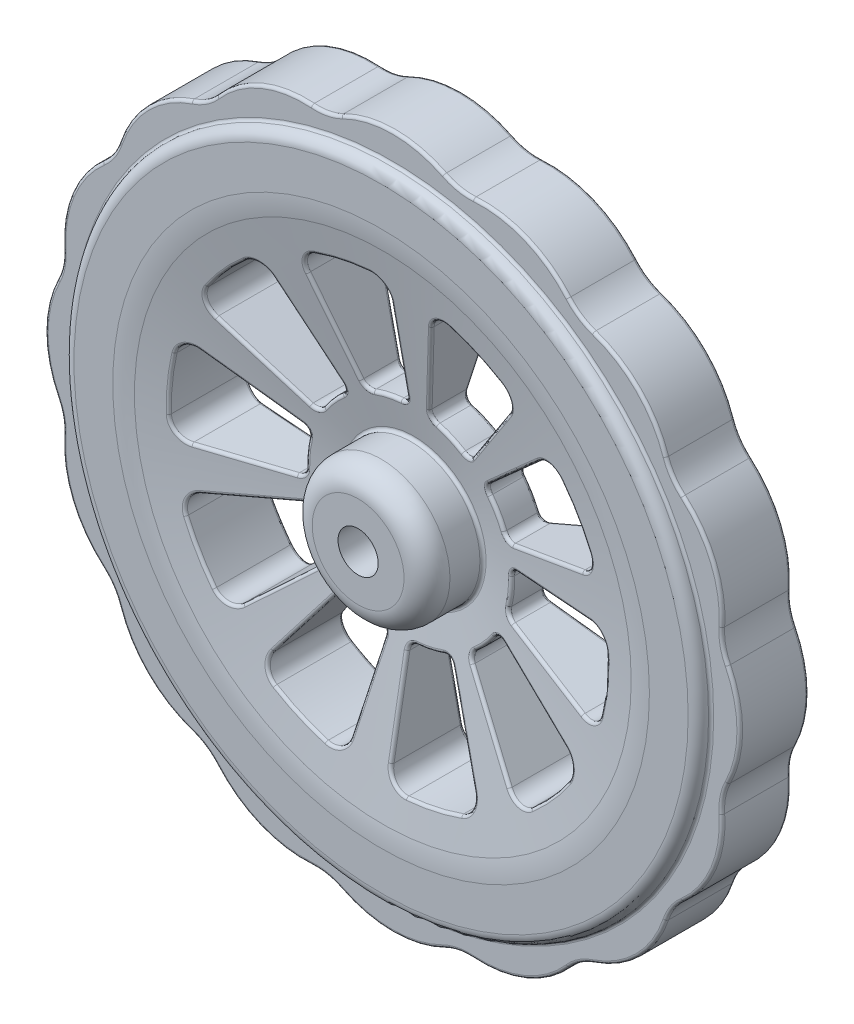
SolidWorks part; units mm, degrees
ref_plane "Alzado" through (0, 0, 0) normal (0, 0, 1) x (1, 0, 0)
ref_plane "Planta" through (0, 0, 0) normal (0, 1, 0) x (1, 0, 0)
ref_plane "Vista lateral" through (0, 0, 0) normal (1, 0, 0) x (0, 0, -1)
sketch "Croquis1" plane through (0, 0, 0) normal (0, 0, 1) x (1, 0, 0)
  circle A1 centre (0, 0) radius 27.75
  dimension "D2" = 55.5
extrude "Saliente-Extruir1" add sketch "Croquis1" along normal blind 8
fillet "Redondeo1" radius 1 2 edges at (27.75, 0, 8) (27.75, 0, 0)
ref_plane "Plano1" through (0, 0, 4) normal (0, 0, 1) x (1, 0, 0)
sketch "Croquis3" plane through (0, 0, 4) normal (0, 0, 1) x (1, 0, 0)
  line L0 (0, 0) -> (0, 10.25) construction
  line L1 (0, 24.3347) -> (0, 27.75) construction
  arc A1 (9.7923, 22.2776) -> (-9.7923, 22.2776) centre (0, 20.25) ccw
  arc A3 (9.7923, 22.2776) -> (-9.7923, 22.2776) centre (0, 0) ccw
  dimension "D1" = 20
extrude "Saliente-Extruir2" add sketch "Croquis3" along normal blind 3 and the other way blind 3
pattern_circular "MatrizC1" count 16 over 360 about axis through (0, 0, 0) along (0, 0, 1) of "Saliente-Extruir2"
fillet "Redondeo2" radius 5 16 edges at (-28.4893, 5.6669, 4) (-28.4893, -5.6669, 4) (-24.1521, -16.1379, 4) (-16.1379, -24.1521, 4) (-5.6669, -28.4893, 4) (5.6669, -28.4893, 4) (16.1379, -24.1521, 4) (24.1521, -16.1379, 4) (28.4893, -5.6669, 4) (28.4893, 5.6669, 4) (24.1521, 16.1379, 4) (16.1379, 24.1521, 4) (5.6669, 28.4893, 4) (-5.6669, 28.4893, 4) (-16.1379, 24.1521, 4) (-24.1521, 16.1379, 4)
sketch "Croquis5" plane through (0, 0, 8) normal (0, 0, 1) x (1, 0, 0)
  circle A0 centre (0, 0) radius 22.5
extrude "Cortar-Extruir1" cut sketch "Croquis5" against normal blind 35 draft 80
sketch "Croquis6" plane through (0, 0, 0) normal (0, 0, -1) x (-1, 0, 0)
  circle A2 centre (0.0467, 0.0871) radius 22.5
  point P5 (0, 0)
  dimension "D1" = 45
extrude "Cortar-Extruir2" cut sketch "Croquis6" against normal blind 35 draft 80
fillet "Redondeo3" radius 10 2 edges at (-22.5467, 0.0871, 0) (22.5, 0, 8)
sketch "Croquis7" plane through (0, 0, 0) normal (0, 0, 1) x (1, 0, 0)
  circle A0 centre (0, 0) radius 6
  dimension "D1" = 12
extrude "Saliente-Extruir4" add sketch "Croquis7" along normal blind 10
sketch "Croquis8" plane through (0, 0, 10) normal (0, 0, 1) x (1, 0, 0)
  circle A0 centre (0, 0) radius 1.75
  dimension "D1" = 3.5
extrude "Cortar-Extruir3" cut sketch "Croquis8" against normal through all
sketch "Croquis9" plane through (0, 0, 8) normal (0, 0, 1) x (1, 0, 0)
  line L0 (-7.2605, 15.9427) -> (-4.0102, 8.8055)
  line L1 (0, 9.6757) -> (0, 17.5181)
  arc A0 (-0.692, 8.9279) -> (-3.0704, 8.4119) centre (0, 0) ccw
  arc A1 (-1.6249, 19.01) -> (-6.4001, 17.9739) centre (0, 0) ccw
  arc A2 (-6.4001, 17.9739) -> (-7.2605, 15.9427) centre (-5.8978, 16.5633) ccw
  arc A3 (0, 17.5181) -> (-1.6249, 19.01) centre (-1.4974, 17.5181) ccw
  arc A4 (-0.692, 8.9279) -> (0, 9.6757) centre (-0.75, 9.6757) ccw
  arc A5 (-4.0102, 8.8055) -> (-3.0704, 8.4119) centre (-3.3276, 9.1164) ccw
  dimension "D1" = 1.5
extrude "Cortar-Extruir4" cut sketch "Croquis9" against normal blind 10
pattern_circular "MatrizC2" count 10 over 360 about axis through (0, 0, 0) along (0, 0, 1) of "Cortar-Extruir4"
fillet "Redondeo4" radius 0.25 66 edges at (-27.9474, -11.5762, 7) (-27.9474, -11.5762, 1) (-21.39, -21.39, 7) (-21.39, -21.39, 1) (-11.5762, -27.9474, 7) (-11.5762, -27.9474, 1) (0, -30.25, 7) (0, -30.25, 1) (11.5762, -27.9474, 7) (11.5762, -27.9474, 1) (21.39, -21.39, 7) (21.39, -21.39, 1) (27.9474, -11.5762, 7) (27.9474, -11.5762, 1) (30.25, 0, 7) (30.25, 0, 1) (27.9474, 11.5762, 7) (27.9474, 11.5762, 1) (21.39, 21.39, 7) (21.39, 21.39, 1) (11.5762, 27.9474, 1) (11.5762, 27.9474, 7) (0, 30.25, 7) (0, 30.25, 1) (-11.5762, 27.9474, 7) (-11.5762, 27.9474, 1) (-21.39, 21.39, 7) (-21.39, 21.39, 1) (-28.7677, 5.7223, 1) (-28.7677, 5.7223, 7) (-28.7677, -5.7223, 1) (-28.7677, -5.7223, 7) (-24.3881, -16.2956, 1) (-24.3881, -16.2956, 7) (-16.2956, -24.3881, 1) (-16.2956, -24.3881, 7) (-5.7223, -28.7677, 1) (-5.7223, -28.7677, 7) (5.7223, -28.7677, 1) (5.7223, -28.7677, 7) (16.2956, -24.3881, 1) (16.2956, -24.3881, 7) (24.3881, -16.2956, 1) (24.3881, -16.2956, 7) (28.7677, -5.7223, 1) (28.7677, -5.7223, 7) (28.7677, 5.7223, 1) (28.7677, 5.7223, 7) (24.3881, 16.2956, 1) (24.3881, 16.2956, 7) (16.2956, 24.3881, 1) (16.2956, 24.3881, 7) (5.7223, 28.7677, 7) (5.7223, 28.7677, 1) (-5.7223, 28.7677, 1) (-5.7223, 28.7677, 7) (-16.2956, 24.3881, 1) (-16.2956, 24.3881, 7) (-24.3881, 16.2956, 1) (-24.3881, 16.2956, 7) (27.75, 0, 1) (27.75, 0, 7) (-30.25, 0, 7) (-30.25, 0, 1) (-27.9474, 11.5762, 7) (-27.9474, 11.5762, 1)
fillet "Redondeo5" radius 0.25 118 edges at (5.5538, 2.2706, 2.9074) (-7.1648, 17.3612, 0.673) (-0.3369, 18.4644, 0.7265) (-0.2435, 9.1226, 2.3738) (-3.6603, 8.4442, 2.3619) (-11.1256, 14.74, 0.7283) (-5.5591, 7.2371, 2.3754) (-7.9246, 4.68, 2.3594) (14.2975, 12.1791, 0.6593) (8.6009, 3.0506, 2.3555) (6.8999, 6.0907, 2.3484) (4.4082, 18.2569, 0.6686) (5.1652, 7.5234, 2.3661) (11.1256, -14.74, 0.6938) (5.5591, -7.2372, 2.341) (7.9247, -4.68, 2.3296) (18.7255, 1.4493, 0.6486) (17.6647, -5.3854, 0.6987) (8.7513, -2.5875, 2.3459) (9.1621, 0.8718, 2.3377) (-18.7256, -1.4492, 0.6626) (-17.6648, 5.3854, 0.7234) (-8.7513, 2.5874, 2.3704) (-9.162, -0.8717, 2.3512) (-14.2976, -12.179, 0.6519) (-17.4566, -6.0263, 0.7138) (-6.8998, -6.0906, 2.3405) (-4.4083, -18.2569, 0.6426) (-10.5805, -15.136, 0.7031) (-5.165, -7.5234, 2.3502) (-2.0022, -8.983, 2.3313) (7.1648, -17.3613, 0.6383) (0.3369, -18.4644, 0.6955) (0.2435, -9.1225, 2.3426) (3.6603, -8.4442, 2.3272) (6, 0, 5.0906) (-0.1686, 9.2019, 5.6555) (0, 13.5969, 6.4301) (-0.675, 18.7694, 7.3443) (-4.0458, 18.6455, 7.3968) (-5.6353, 12.3741, 6.4301) (-3.5593, 8.4031, 5.6418) (-1.8989, 8.7511, 5.6116) (-5.5451, 7.3454, 5.6555) (-7.9921, 11.0001, 6.4301) (-11.5785, 14.788, 7.3443) (-14.2326, 12.7064, 7.3968) (-7.8187, 4.7061, 5.6418) (-6.68, 5.9636, 5.6116) (17.6422, 6.442, 7.3443) (16.4827, 9.6095, 7.3968) (13.8441, 12.2224, 7.2889) (7.736, 4.5101, 5.6116) (5.2723, 7.5436, 5.6555) (7.9921, 11.0001, 6.4301) (10.4863, 15.5816, 7.3443) (4.016, 18.0255, 7.289) (2.7143, 13.3232, 6.4301) (2.0597, 8.8903, 5.6418) (3.6075, 8.1959, 5.6116) (5.5451, -7.3454, 5.6555) (11.5785, -14.788, 7.3443) (14.2326, -12.7064, 7.3968) (11.8324, -6.6985, 6.4301) (7.8187, -4.7061, 5.6418) (8.8036, -2.6832, 5.6555) (12.9314, -4.2017, 6.4301) (18.9831, -1.914, 7.3968) (18.3843, 1.7507, 7.289) (13.5099, 1.5357, 6.4301) (8.9095, -0.8983, 5.6116) (-8.8036, 2.6832, 5.6555) (-12.9314, 4.2017, 6.4301) (-18.0594, 5.1581, 7.3443) (-13.5099, -1.5357, 6.4301) (-8.9095, 0.8983, 5.6116) (-8.6994, -3.0039, 5.6555) (-12.9314, -4.2017, 6.4301) (-17.6422, -6.442, 7.3443) (-16.4827, -9.6095, 7.3968) (-13.8441, -12.2224, 7.2889) (-10.0271, -9.1833, 6.4301) (-6.8919, -5.9817, 5.6418) (-5.2723, -7.5436, 5.6555) (-7.6864, -17.4626, 7.3968) (-4.016, -18.0255, 7.289) (-3.6075, -8.1959, 5.6116) (0.1686, -9.2019, 5.6555) (0, -13.5969, 6.4301) (5.6353, -12.3741, 6.4301) (3.5593, -8.4031, 5.6418) (1.8989, -8.7511, 5.6116)
fillet "Redondeo6" radius 1 1 edges at (6, 0, 0)
fillet "Redondeo7" radius 2 1 edges at (6, 0, 10)
